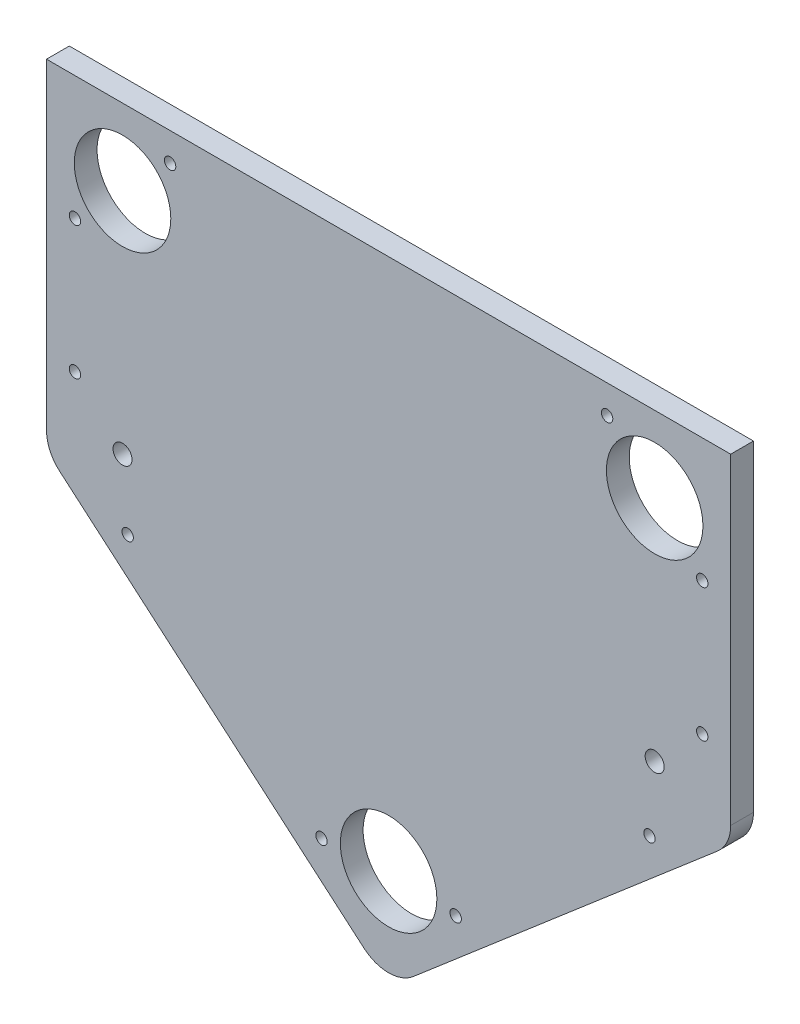
SolidWorks part; units mm, degrees
ref_plane "Front Plane" through (0, 0, 0) normal (0, 0, 1) x (1, 0, 0)
ref_plane "Top Plane" through (0, 0, 0) normal (0, 1, 0) x (1, 0, 0)
ref_plane "Right Plane" through (0, 0, 0) normal (1, 0, 0) x (0, 0, -1)
sketch "Sketch1" plane through (0, 0, 0) normal (0, 0, 1) x (1, 0, 0)
  line L0 (-70, 60) -> (70, 60) construction
  line L1 (-70, 0) -> (70, 0) construction
  line L2 (-82.5158, 47.4842) -> (-70, 60) construction
  line L3 (0, -60) -> (-70, 0) construction
  line L4 (0, -60) -> (-17.6479, -61.3575) construction
  line L5 (-68.6425, -17.6479) -> (-70, 0) construction
  line L6 (0, -60) -> (0, 60) construction
  line L7 (-90, 80) -> (90, 80)
  line L8 (90, 80) -> (90, -9.1987)
  line L9 (90, -9.1987) -> (0, -86.3416)
  line L10 (0, -86.3416) -> (-90, -9.1987)
  line L11 (-90, -9.1987) -> (-90, 80)
  circle A0 centre (-70, 60) radius 12.7
  circle A1 centre (70, 60) radius 12.7
  circle A2 centre (-70, 0) radius 2.5
  circle A3 centre (70, 0) radius 2.5
  circle A4 centre (0, -60) radius 12.7
  circle A5 centre (-82.5158, 47.4842) radius 1.5
  circle A6 centre (-57.4842, 72.5158) radius 1.5
  circle A7 centre (-82.5158, 12.5158) radius 1.5
  circle A8 centre (-68.6425, -17.6479) radius 1.5
  circle A9 centre (-17.6479, -61.3575) radius 1.5
  circle A10 centre (-70, 0) radius 12.7 construction
  circle A11 centre (70, 0) radius 12.7 construction
  circle A12 centre (-70, 0) radius 17.7 construction
  circle A13 centre (-70, 60) radius 17.7 construction
  circle A14 centre (0, -60) radius 17.7 construction
  circle A15 centre (17.6479, -61.3575) radius 1.5
  circle A16 centre (68.6425, -17.6479) radius 1.5
  circle A17 centre (82.5158, 12.5158) radius 1.5
  circle A18 centre (82.5158, 47.4842) radius 1.5
  circle A19 centre (57.4842, 72.5158) radius 1.5
  point P12 (0, 60)
  point P43 (0, 0)
  point P45 (0, 80)
  point P46 (-90, -22.9392)
  dimension "D1" = 25.4
  dimension "D2" = 5
  dimension "D5" = 3
  dimension "D3" = 60
  dimension "D4" = 60
  dimension "D6" = 5
  dimension "D7" = 135
  dimension "D8" = 45
  dimension "D9" = 140
  dimension "D10" = 45
  dimension "D11" = 20
  dimension "D12" = 20
  dimension "D13" = 20
  dimension "D14" = 20
  dimension "D15" = 20
extrude "Boss-Extrude1" add sketch "Sketch1" along normal blind 6
fillet "Fillet1" radius 10 3 edges at (-90, -9.1987, 3) (90, -9.1987, 3) (0, -86.3416, 3)
equation "\"carbon_fiber_tube_diam\"= 1in"
equation "\"clip_tube_diam\"= 6mm"
equation "\"D1@Sketch1\"=\"carbon_fiber_tube_diam\""
